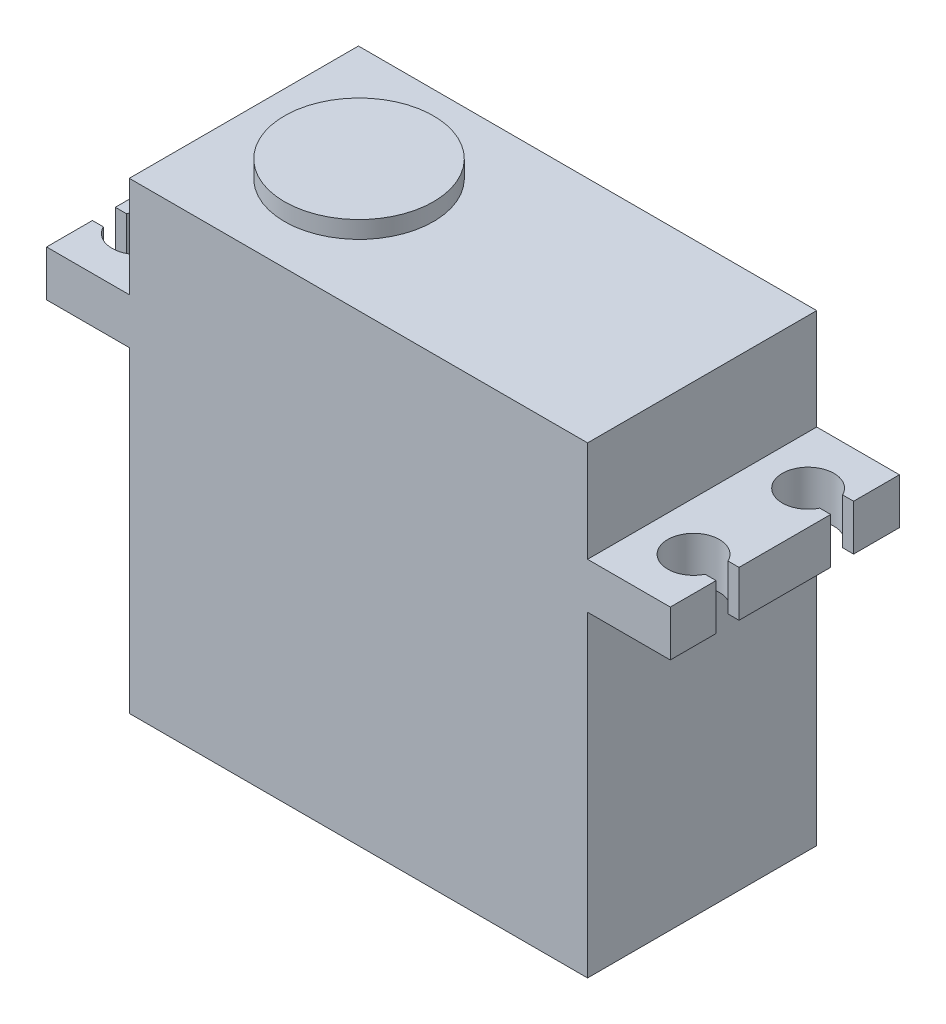
SolidWorks part; units mm, degrees
ref_plane "Front Plane" through (0, 0, 0) normal (0, 0, 1) x (1, 0, 0)
ref_plane "Top Plane" through (0, 0, 0) normal (0, 1, 0) x (1, 0, 0)
ref_plane "Right Plane" through (0, 0, 0) normal (1, 0, 0) x (0, 0, -1)
sketch "Sketch2" plane through (0, 0, 0) normal (0, 1, 0) x (1, 0, 0)
  line L1 (-20, -10) -> (20, -10)
  line L2 (-20, -10) -> (-20, 10)
  line L3 (-20, 10) -> (20, 10)
  line L4 (20, -10) -> (20, 10)
  line L5 (-20, -10) -> (20, 10) construction
  line L6 (-20, 10) -> (20, -10) construction
  point P0 (0, 0)
  dimension "D1" = 20
  dimension "D2" = 40
extrude "Boss-Extrude1" add sketch "Sketch2" along normal blind 27.65
sketch "Sketch3" plane through (-20, 0, 0) normal (-1, 0, 0) x (0, 0, 1)
  line L0 (0, 0) -> (0, 4) construction
  line L1 (-10, 0) -> (10, 0) construction
  line L3 (-3.5, 8) -> (3.5, 8)
  line L4 (-3.5, 8) -> (-3.5, 4)
  line L5 (-3.5, 4) -> (3.5, 4)
  line L6 (3.5, 8) -> (3.5, 4)
  line L7 (-3.5, 8) -> (3.5, 4) construction
  line L8 (-3.5, 4) -> (3.5, 8) construction
  point P4 (0, 6)
  dimension "D1" = 4
  dimension "D2" = 7
extrude "Boss-Extrude2" add sketch "Sketch3" along normal blind 5
sketch "Sketch5" plane through (0, 27.65, 0) normal (0, 1, 0) x (1, 0, 0)
  line L4 (20, -10) -> (20, 10)
  line L5 (20, 10) -> (-20, 10)
  line L6 (-20, 10) -> (-20, -10)
  line L7 (-20, -10) -> (20, -10)
  line L8 (20, -10) -> (20, 10)
  line L9 (20, 10) -> (-20, 10)
  line L10 (-20, 10) -> (-20, -10)
  line L11 (-20, -10) -> (20, -10)
  dimension "D1" = 0
extrude "Boss-Extrude5" add sketch "Sketch5" along normal blind 12.8
sketch "Sketch7" plane through (-20, 0, 0) normal (-1, 0, 0) x (0, 0, 1)
  line L0 (-10, 27.65) -> (10, 27.65)
  line L1 (10, 27.65) -> (10, 31.65)
  line L2 (10, 40.45) -> (10, 0) construction
  line L3 (-10, 31.65) -> (-10, 27.65)
  line L4 (-10, 40.45) -> (-10, 0) construction
  line L5 (10, 31.65) -> (-10, 31.65)
  dimension "D1" = 4
extrude "Boss-Extrude6" add sketch "Sketch7" along normal blind 7.22
sketch "Sketch8" plane through (0, 31.65, 0) normal (0, 1, 0) x (1, 0, 0)
  line L0 (-20, 10) -> (-20, 0) construction
  line L1 (-20, 0) -> (-27.22, 0) construction
  line L2 (-27.22, -10) -> (-27.22, 10) construction
  line L3 (-20, 5) -> (-27.22, 5) construction
  line L4 (-26.2656, 6) -> (-27.22, 6)
  line L8 (-27.22, 6) -> (-27.22, 4)
  line L9 (-27.22, 4) -> (-26.2656, 4)
  arc A1 (-26.2656, 4) -> (-26.2656, 6) centre (-24.25, 5) ccw
  dimension "D1" = 4.25
  dimension "D3" = 4.5
  dimension "D2" = 1
extrude "Cut-Extrude3" cut sketch "Sketch8" against normal blind 4
mirror "Mirror10" about plane through (0, 0, 0) normal (0, 0, 1) of "Cut-Extrude3"
mirror "Mirror11" about plane through (0, 0, 0) normal (1, 0, 0) of "Mirror10", "Cut-Extrude3", "Boss-Extrude6"
sketch "Sketch9" plane through (0, 40.45, 0) normal (0, 1, 0) x (1, 0, 0)
  line L0 (20, 0) -> (-20, 0) construction
  line L1 (20, -10) -> (20, 10) construction
  line L2 (-20, 10) -> (-20, -10) construction
  line L5 (-9.95, 0) -> (-9.95, 8.0914) construction
  circle A1 centre (-9.95, 0) radius 6.5
  circle A2 centre (-9.95, 0) radius 3
  dimension "D1" = 13
  dimension "D3" = 6
  dimension "D2" = 29.95
extrude "Boss-Extrude8" add sketch "Sketch9" along normal blind 1.5 contours A1 A2 | A2 region at (-16.2662, 40.45, 0)
sketch "Sketch10" plane through (0, 31.65, 0) normal (0, 1, 0) x (1, 0, 0)
  circle A0 centre (24, 5) radius 2 construction
  circle A1 centre (24, -5) radius 2 construction
  circle A2 centre (-24, 5) radius 2 construction
  circle A3 centre (-24, -5) radius 2 construction
